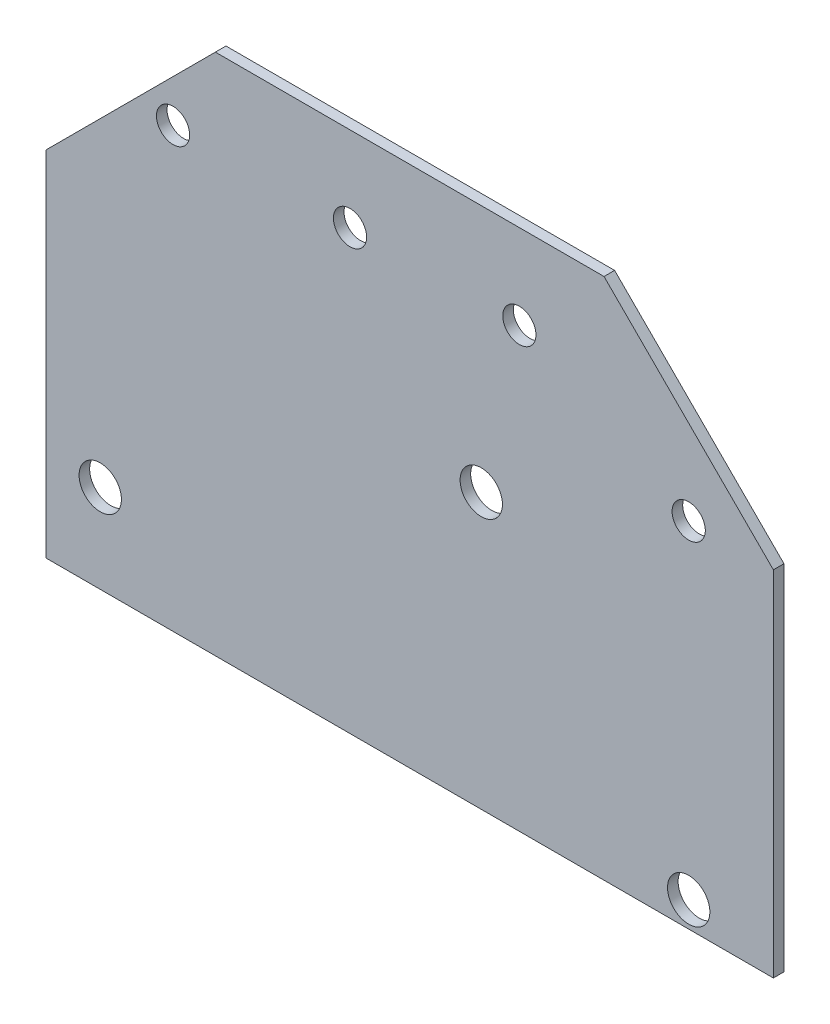
SolidWorks part; units mm, degrees
ref_plane "Front Plane" through (0, 0, 0) normal (0, 0, 1) x (1, 0, 0)
ref_plane "Top Plane" through (0, 0, 0) normal (0, 1, 0) x (1, 0, 0)
ref_plane "Right Plane" through (0, 0, 0) normal (1, 0, 0) x (0, 0, -1)
sketch "Sketch1" plane through (0, 0, 0) normal (0, 0, 1) x (1, 0, 0)
  line L0 (233.807, -12.7) -> (233.807, -65.7225)
  line L1 (317.5, 12.7) -> (-317.5, 12.7) construction
  line L3 (342.9, -65.7225) -> (342.9, -12.7)
  line L4 (317.5, 12.7) -> (259.207, 12.7)
  line L5 (342.9, -214.3125) -> (342.9, 446.0875) construction
  line L6 (262.8977, -93.6625) -> (262.8977, -65.7225) construction
  line L7 (260.35, -93.6625) -> (330.2, -93.6625) construction
  line L8 (342.9, -12.7) -> (317.5, 12.7)
  line L9 (233.807, -65.7225) -> (342.9, -65.7225)
  line L10 (259.207, 12.7) -> (233.807, -12.7)
  circle A0 centre (227.457, 0) radius 6.35 construction
  point P0 (233.807, 12.7)
  point P6 (342.9, 12.7)
  dimension "D1" = 27.94
extrude "Boss-Extrude1" add sketch "Sketch1" along normal blind 1.5875
hole_wizard "#10 Clearance Hole1" positions "Sketch2" profile "Sketch3" hole size "#10" standard "ANSI Inch" end condition through all
sketch "Sketch2" plane through (0, 0, 0) normal (0, 0, -1) x (-1, 0, 0)
  point P0 (-330.2, -12.7)
  point P3 (-304.8, 0)
  point P6 (-279.4, 0)
  point P9 (-252.857, 0)
sketch "Sketch3" plane through (330.2, -12.7, 0) normal (1, 0, 0) x (0, 1, 0)
  line L0 (0, 0) -> (0, 1.5875)
  line L1 (0, 1.5875) -> (2.4892, 1.5875)
  line L2 (2.4892, 1.5875) -> (2.4892, 0)
  line L5 (2.4892, 0) -> (0, 0)
  line L11 (0, -6.35) -> (0, 107.95) construction
  dimension "Thru Hole Dia." = 4.9784
  dimension "Thru Hole Depth" = 1.5875
hole_wizard "1/4 (0.25) Diameter Hole1" positions "Sketch4" profile "Sketch5" hole size "1/4" standard "ANSI Inch" end condition through all
sketch "Sketch4" plane through (0, 0, 0) normal (0, 0, -1) x (-1, 0, 0)
  point P0 (-330.2, -61.9125)
sketch "Sketch5" plane through (330.2, -61.9125, 0) normal (1, 0, 0) x (0, 1, 0)
  line L0 (0, 0) -> (0, 1.5875)
  line L1 (0, 1.5875) -> (3.175, 1.5875)
  line L2 (3.175, 1.5875) -> (3.175, 0)
  line L5 (3.175, 0) -> (0, 0)
  line L11 (0, -6.35) -> (0, 107.95) construction
  dimension "Thru Hole Dia." = 6.35
  dimension "Thru Hole Depth" = 1.5875
hole_wizard "1/4 (0.25) Diameter Hole2" positions "Sketch6" profile "Sketch7" hole size "1/4" standard "ANSI Inch" end condition through all
sketch "Sketch6" plane through (0, 0, 1.5875) normal (0, 0, 1) x (1, 0, 0)
  point P0 (299.085, -24.5252)
  point P3 (241.935, -52.4652)
sketch "Sketch7" plane through (299.085, -24.5252, 1.5875) normal (1, 0, 0) x (0, -1, 0)
  line L0 (0, 0) -> (0, 1.5875)
  line L1 (0, 1.5875) -> (3.175, 1.5875)
  line L2 (3.175, 1.5875) -> (3.175, 0)
  line L5 (3.175, 0) -> (0, 0)
  line L11 (0, -6.35) -> (0, 107.95) construction
  dimension "Thru Hole Dia." = 6.35
  dimension "Thru Hole Depth" = 1.5875
